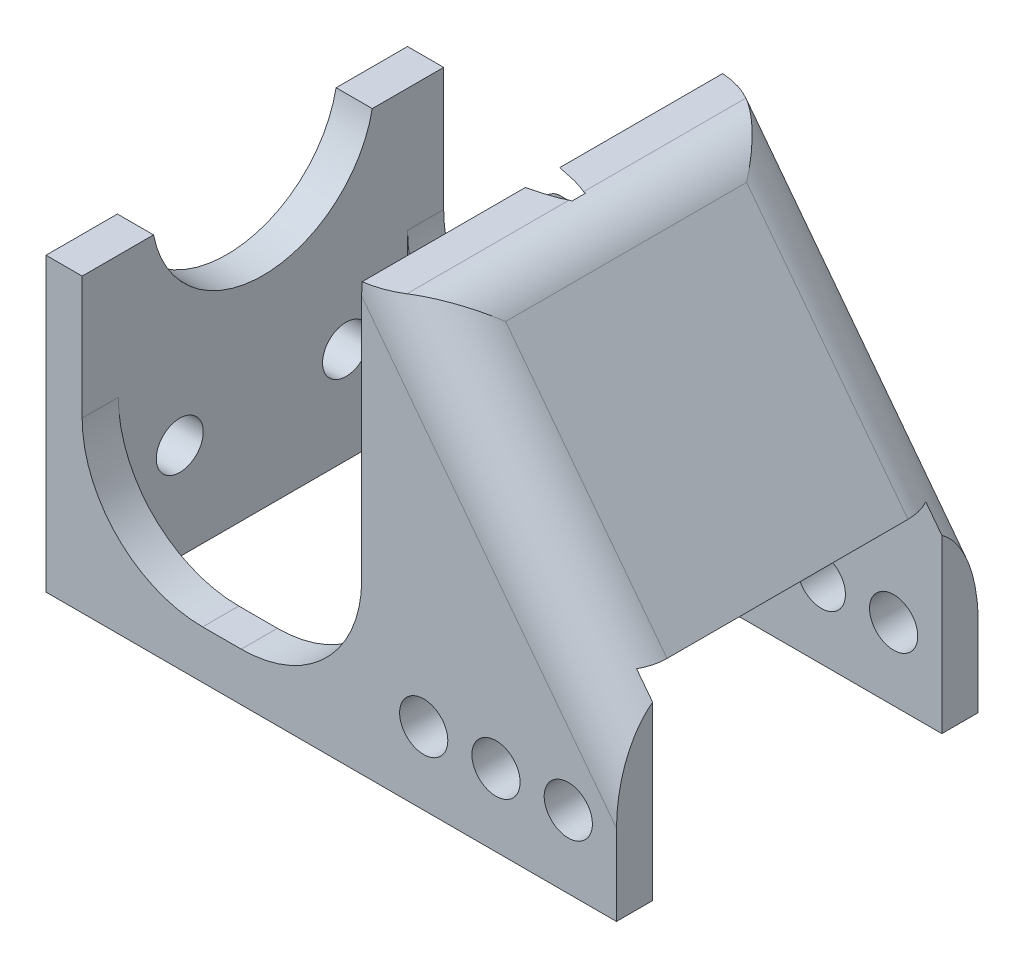
SolidWorks part; units mm, degrees
ref_plane "Front Plane" through (0, 0, 0) normal (0, 0, 1) x (1, 0, 0)
ref_plane "Top Plane" through (0, 0, 0) normal (0, 1, 0) x (1, 0, 0)
ref_plane "Right Plane" through (0, 0, 0) normal (1, 0, 0) x (0, 0, -1)
sketch "Sketch1" plane through (0, 0, 0) normal (0, 0, 1) x (1, 0, 0)
  line L0 (0, 0) -> (-10, -13.0323) construction
  line L1 (0, 0) -> (10, -13.0323) construction
  line L2 (-10, -13.0323) -> (10, -13.0323)
  line L9 (-11.1437, 22.3593) -> (-5.7608, 22.5296)
  line L10 (-11.1437, -9.0323) -> (-11.1437, 22.3593)
  line L11 (10, 1.9125) -> (10, -13.0323)
  line L12 (-5.7608, 22.5296) -> (10, 1.9125)
  line L13 (-10, -13.0323) -> (-37.3437, -13.0323)
  line L14 (-37.3437, -13.0323) -> (-37.3437, 11.1805)
  line L15 (-37.3437, 11.1805) -> (-34.3437, 11.1805)
  line L16 (-34.3437, 11.1805) -> (-34.3437, -9.0323)
  line L17 (-11.1437, -9.0323) -> (-34.3437, -9.0323)
  circle A2 centre (0, -7.0323) radius 2
  circle A3 centre (6, -7.0323) radius 2
  circle A4 centre (-6, -7.0323) radius 2
  dimension "D6" = 4
  dimension "D7" = 4
  dimension "D10" = 4
  dimension "D1" = 75
  dimension "D2" = 20
  dimension "D3" = 35.41
  dimension "D4" = 23.2
  dimension "D5" = 6
  dimension "D8" = 6
  dimension "D9" = 6
  dimension "D11" = 3
  dimension "D12" = 4
extrude "Boss-Extrude1" add sketch "Sketch1" along normal blind 30
sketch "Sketch2" plane through (10, 0, 0) normal (1, 0, 0) x (0, 0, -1)
  line L1 (-27, -13.0323) -> (-3, -13.0323)
  line L2 (-27, -13.0323) -> (-27, 2.9677)
  line L3 (-27, 2.9677) -> (-3, 2.9677)
  line L4 (-3, -13.0323) -> (-3, 2.9677)
  line L5 (-30, -13.0323) -> (0, -13.0323) construction
  dimension "D1" = 16
extrude "Cut-Extrude1" cut sketch "Sketch2" against normal up to surface (44.3437 mm away) up to face at (-34.3437, 1.0741, 15)
sketch "Sketch3" plane through (-11.1437, 0, 0) normal (-1, 0, 0) x (0, 0, 1)
  line L0 (3, 2.9677) -> (27, 2.9677) construction
  circle A0 centre (15, 12.9677) radius 9.5
  circle A1 centre (15, 12.9677) radius 6 construction
  circle A2 centre (15, 18.9677) radius 2
  circle A3 centre (15, 6.9677) radius 2
  circle A4 centre (9, 12.9677) radius 2
  circle A5 centre (21, 12.9677) radius 2
  point P5 (15, 2.9677)
  dimension "D1" = 19
  dimension "D2" = 10
  dimension "D3" = 12
  dimension "D4" = 4
  dimension "D5" = 4
  dimension "D6" = 4
  dimension "D7" = 4
extrude "Cut-Extrude2" cut sketch "Sketch3" against normal blind 3
fillet "Fillet1" [suppressed] radius 2
sketch "Sketch4" plane through (-34.3437, 0, 0) normal (1, 0, 0) x (0, 0, -1)
  circle A0 centre (-15, 12.9677) radius 2 construction
  arc A1 (-17, 12.9677) -> (-13, 12.9677) centre (-15, 12.9677) ccw construction
  arc A2 (-17, 12.9677) -> (-13, 12.9677) centre (-15, 12.9677) ccw construction
  circle A3 centre (-15, 12.9677) radius 9.25
  dimension "D1" = 4
  dimension "D2" = 18.5
extrude "Cut-Extrude3" cut sketch "Sketch4" against normal through all
fillet "Fillet2" radius 10 4 edges at (-11.1437, -9.0323, 1.5) (-11.1437, -9.0323, 28.5) (-34.3437, -9.0323, 28.5) (-34.3437, -9.0323, 1.5)
fillet "Fillet3" radius 5 3 edges at (-5.7608, 22.5296, 15) (2.1196, 12.2211, 30) (2.1196, 12.2211, 0)
hole_wizard "M3.5 Clearance Hole1" positions "Sketch5" profile "Sketch6" hole size "M3.5" standard "ANSI Metric" end condition through all
sketch "Sketch5" plane through (-37.3437, 0, 0) normal (-1, 0, 0) x (0, 0, 1)
  point P0 (8.1, -5.0323)
  point P3 (21.9, -5.0323)
sketch "Sketch6" plane through (-37.3437, -5.0323, 8.1) normal (0, 1, 0) x (0, 0, 1)
  line L0 (0, 0) -> (0, 47.3437)
  line L1 (0, 47.3437) -> (1.95, 47.3437)
  line L2 (1.95, 47.3437) -> (1.95, 0.025)
  line L3 (1.95, 0.025) -> (1.975, 0)
  line L5 (1.975, 0) -> (0, 0)
  line L6 (-1.95, 0.025) -> (-1.975, 0) construction
  line L11 (0, -6.35) -> (0, 107.95) construction
  dimension "Thru Hole Dia." = 3.9
  dimension "Thru Hole Depth" = 47.3437
  dimension "Near C'Sink Dia." = 3.95
  dimension "Near C'Sink Angle" = 90
